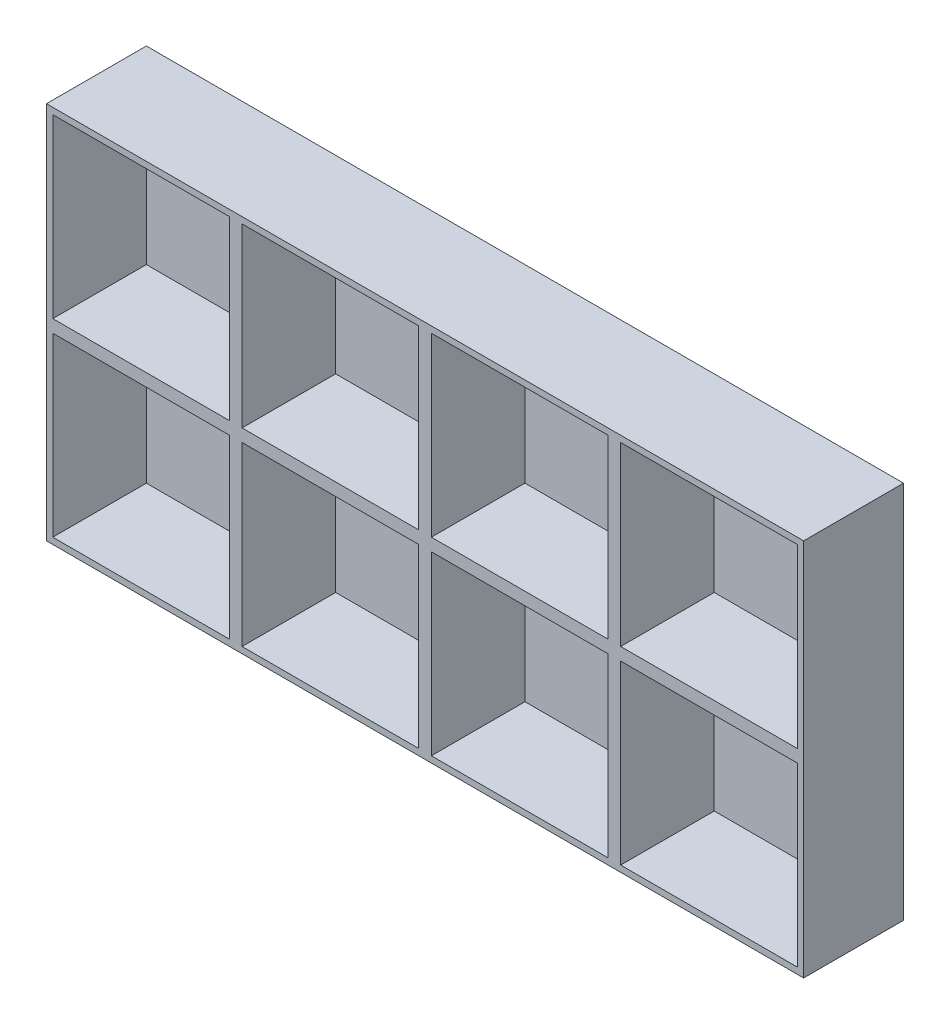
SolidWorks part; units mm, degrees
ref_plane "Plan de face" through (0, 0, 0) normal (0, 0, 1) x (1, 0, 0)
ref_plane "Plan de dessus" through (0, 0, 0) normal (0, 1, 0) x (1, 0, 0)
ref_plane "Plan de droite" through (0, 0, 0) normal (1, 0, 0) x (0, 0, -1)
sketch "Esquisse1" plane through (0, 0, 0) normal (0, 0, 1) x (1, 0, 0)
  line L0 (0, 0) -> (0, 30)
  line L16 (59, 1) -> (59, 29)
  line L17 (59, 29) -> (31, 29)
  line L18 (31, 29) -> (31, 1)
  line L20 (29, 1) -> (29, 29)
  line L21 (29, 29) -> (1, 29)
  line L22 (1, 29) -> (1, 1)
  line L24 (0, 30) -> (120, 30)
  line L25 (60, 30) -> (60, 1) construction
  line L27 (119, 29) -> (119, 1)
  line L28 (91, 29) -> (119, 29)
  line L29 (91, 1) -> (91, 29)
  line L31 (89, 29) -> (89, 1)
  line L32 (61, 29) -> (89, 29)
  line L33 (61, 1) -> (61, 29)
  line L34 (120, 0) -> (120, 30)
  line L35 (0, 0) -> (120, 0)
  line L36 (1, 1) -> (29, 1)
  line L37 (29, 29) -> (31, 29) construction
  line L38 (59, 29) -> (61, 29) construction
  line L39 (89, 29) -> (91, 29) construction
  line L41 (119, 1) -> (120, 1) construction
  line L42 (91, 1) -> (119, 1)
  line L43 (61, 1) -> (89, 1)
  line L44 (31, 1) -> (59, 1)
  dimension "D1" = 1
  dimension "D2" = 1
  dimension "D3" = 2
  dimension "D4" = 30
  dimension "D5" = 1
  dimension "D6" = 28
  dimension "D7" = 28
extrude "Boss.-Extru.1" add sketch "Esquisse1" along normal blind 14.8333 contours L0 L35 L34 L24 L44 L18 L17 L16 L43 L33 L32 L31 L42 L29 L28 L27 L36 L22 L21 L20 region at (60, 15, 0)
mirror "Symétrie1" about plane through (0, 0, 14.8333) normal (0, 1, 0) of "Boss.-Extru.1"
sketch "Esquisse2" plane through (0, 0, 0) normal (0, 0, -1) x (-1, 0, 0)
  line L1 (-120, 30) -> (0, 30)
  line L2 (-120, 30) -> (-120, -30)
  line L3 (-120, -30) -> (0, -30)
  line L4 (0, 30) -> (0, -30)
extrude "Boss.-Extru.2" add sketch "Esquisse2" along normal blind 1
